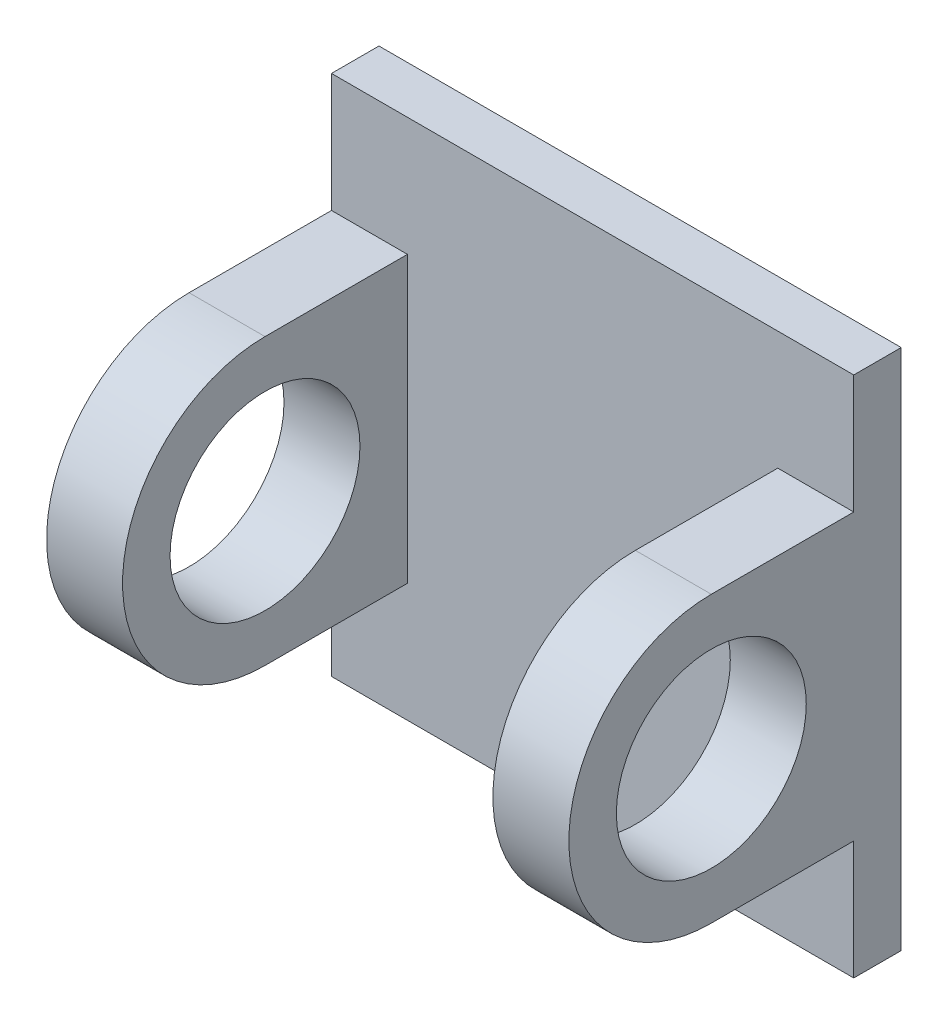
SolidWorks part; units mm, degrees
material "PLA"
ref_plane "Front Plane" through (0, 0, 0) normal (1, 0, 0) x (0, 1, 0)
ref_plane "Top Plane" through (0, 0, 0) normal (0, 0, 1) x (0, 1, 0)
ref_plane "Right Plane" through (0, 0, 0) normal (0, 1, 0) x (-1, 0, 0)
sketch "Sketch1" plane through (0, 0, 0) normal (0, 0, 1) x (0, 1, 0)
  line L1 (-13.75, -13.75) -> (13.75, -13.75)
  line L2 (-13.75, -13.75) -> (-13.75, 13.75)
  line L3 (-13.75, 13.75) -> (13.75, 13.75)
  line L4 (13.75, -13.75) -> (13.75, 13.75)
  line L5 (-13.75, -13.75) -> (13.75, 13.75) construction
  line L6 (-13.75, 13.75) -> (13.75, -13.75) construction
  point P0 (0, 0)
  dimension "D1" = 27.5
extrude "Boss-Extrude1" add sketch "Sketch1" along normal blind 2.5
sketch "Sketch2" plane through (13.75, 0, 0) normal (1, 0, 0) x (0, 1, 0)
  line L0 (-7.5, 2.5) -> (7.5, 2.5)
  line L1 (-13.75, 2.5) -> (13.75, 2.5) construction
  line L2 (7.5, 2.5) -> (7.5, 10)
  line L3 (-7.5, 2.5) -> (-7.5, 10)
  arc A0 (7.5, 10) -> (-7.5, 10) centre (0, 10) ccw
  circle A1 centre (0, 10) radius 5
  point P5 (0, 2.5)
  dimension "D1" = 10
  dimension "D2" = 2.5
  dimension "D3" = 7.5
extrude "Boss-Extrude2" add sketch "Sketch2" against normal blind 27.5
sketch "Sketch3" plane through (0, 0, 0) normal (1, 0, 0) x (0, 1, 0)
  line L1 (-13.75, 2.5) -> (13.75, 2.5)
  line L2 (-13.75, 2.5) -> (-13.75, 18.2629)
  line L3 (-13.75, 18.2629) -> (13.75, 18.2629)
  line L4 (13.75, 2.5) -> (13.75, 18.2629)
extrude "Cut-Extrude1" cut sketch "Sketch3" against normal offset from surface 4 and the other way offset from surface 4 up to face at (-13.75, 0, 4.6875) other way up to face at (13.75, 0, 4.6875)
sketch "Sketch4" plane through (0, 13.75, 0) normal (0, 1, 0) x (-1, 0, 0)
  line L1 (-13.75, 0) -> (13.75, 0)
  line L2 (-13.75, 0) -> (-13.75, 2.5)
  line L3 (-13.75, 2.5) -> (13.75, 2.5)
  line L4 (13.75, 0) -> (13.75, 2.5)
extrude "Cut-Extrude2" [suppressed] cut sketch "Sketch4" against normal up to surface (7.0945 mm away) up to face at (11.75, 7.5, 6.25)
sketch "Sketch5" plane through (0, -13.75, 0) normal (0, -1, 0) x (1, 0, 0)
  line L1 (-13.75, 0) -> (13.75, 0)
  line L2 (-13.75, 0) -> (-13.75, 2.5)
  line L3 (-13.75, 2.5) -> (13.75, 2.5)
  line L4 (13.75, 0) -> (13.75, 2.5)
extrude "Cut-Extrude3" [suppressed] cut sketch "Sketch5" against normal up to surface (5.4055 mm away) up to face at (-11.75, -7.5, 6.25)
equation "\"ball_diameter\"= 0.75in"
equation "\"wall_thickness\" = 0.25cm"
equation "\"track_length\" = 25cm"
equation "\"axle\" = 5mm"
equation "\"pillar_width\" = 2.75cm"
equation "\"D1@Sketch1\"=\"pillar_width\""
equation "\"D1@Boss-Extrude1\"=\"wall_thickness\""
